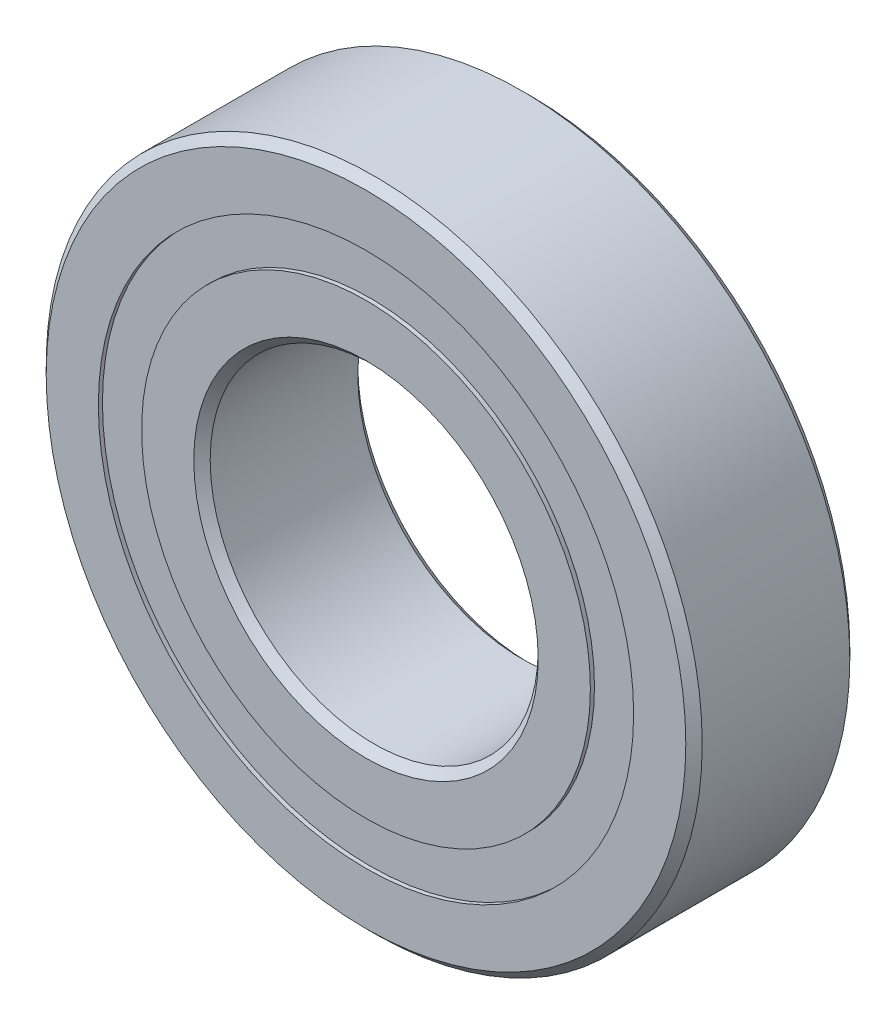
SolidWorks part; units mm, degrees
material "AISI 304"
ref_plane "Front Plane" through (0, 0, 0) normal (0, 0, 1) x (1, 0, 0)
ref_plane "Top Plane" through (0, 0, 0) normal (0, 1, 0) x (1, 0, 0)
ref_plane "Right Plane" through (0, 0, 0) normal (1, 0, 0) x (0, 0, -1)
sketch "Sketch1" plane through (0, 0, 0) normal (1, 0, 0) x (0, 0, -1)
  line L0 (-6.35, 0) -> (6.35, 0) construction
  line L1 (0, 25.4) -> (0, -25.4) construction
  line L2 (5.715, 25.4) -> (-5.715, 25.4)
  line L3 (-5.715, 25.4) -> (-6.35, 24.765)
  line L4 (-6.35, 24.765) -> (-6.35, 20.7247)
  line L5 (-6.35, 20.7247) -> (-2.8222, 20.7247)
  line L6 (6.35, 20.7247) -> (2.8222, 20.7247)
  line L7 (6.35, 24.765) -> (6.35, 20.7247)
  line L8 (5.715, 25.4) -> (6.35, 24.765)
  line L9 (0, 25.4) -> (0, 19.05) construction
  line L10 (0, 19.05) -> (0, 12.7) construction
  arc A0 (-2.8222, 20.7247) -> (2.8222, 20.7247) centre (0, 19.05) cw
  point P14 (0, 12.7)
  dimension "Width" = 12.7
  dimension "OD" = 50.8
  dimension "D1" = 45
  dimension "D2" = 0.635
  dimension "Shaft Dia" = 25.4
  dimension "D3" = 5.6444
  dimension "D4" = 1.6747
revolve "Revolve1" add sketch "Sketch1" angle 360 about L0
sketch "Sketch3" plane through (0, 0, 0) normal (1, 0, 0) x (0, 0, -1)
  line L0 (-6.35, 17.3753) -> (-2.8222, 17.3753)
  line L1 (0, 25.4) -> (0, -25.4) construction
  line L2 (-6.35, 24.765) -> (-6.35, 20.7247) construction
  line L3 (-6.35, 17.3753) -> (-6.35, 13.335)
  line L4 (-5.715, 25.4) -> (-6.35, 24.765) construction
  line L5 (-6.35, 13.335) -> (-5.715, 12.7)
  line L6 (-5.715, 12.7) -> (5.715, 12.7)
  line L7 (5.715, 25.4) -> (5.715, -25.4) construction
  line L8 (5.715, 12.7) -> (6.35, 13.335)
  line L9 (6.35, -24.765) -> (6.35, 24.765) construction
  line L10 (6.35, 13.335) -> (6.35, 17.3753)
  line L11 (6.35, 17.3753) -> (2.8222, 17.3753)
  line L13 (5.715, 25.4) -> (6.35, 24.765) construction
  arc A0 (2.8222, 20.7247) -> (-2.8222, 20.7247) centre (0, 19.05) ccw construction
  arc A1 (2.8222, 17.3753) -> (-2.8222, 17.3753) centre (0, 19.05) cw
revolve "Revolve3" add sketch "Sketch3" angle 360 about L0
sketch "Sketch4" plane through (0, 0, 0) normal (1, 0, 0) x (0, 0, -1)
  line L0 (-3.2817, 19.05) -> (3.2817, 19.05)
  arc A2 (-3.2817, 19.05) -> (3.2817, 19.05) centre (0, 19.05) cw
  arc A3 (2.8222, 20.7247) -> (-2.8222, 20.7247) centre (0, 19.05) ccw construction
revolve "Revolve4" add sketch "Sketch4" angle 360 about L0
ref_axis "Axis1" through (0, 0, -6.35) along (0, 0, 1)
pattern_circular "CirPattern1" count 12 every 30 about axis through (0, 0, -6.35) along (0, 0, 1) of bodies 104
sketch "Sketch5" plane through (0, 0, 0) normal (1, 0, 0) x (0, 0, -1)
  line L0 (-6.35, 20.7247) -> (-2.8222, 20.7247) construction
  line L1 (-6.0325, 20.7247) -> (-3.2817, 20.7247)
  line L2 (-6.0325, 20.7247) -> (-6.0325, 17.3753)
  line L3 (-6.0325, 17.3753) -> (-3.2817, 17.3753)
  line L4 (-3.2817, 20.7247) -> (-3.2817, 17.3753)
  line L5 (-6.35, 17.3753) -> (-2.8222, 17.3753) construction
  line L6 (6.35, 20.7247) -> (2.8222, 20.7247) construction
  line L7 (6.0325, 20.7247) -> (3.2817, 20.7247)
  line L8 (6.0325, 20.7247) -> (6.0325, 17.3753)
  line L9 (6.0325, 17.3753) -> (3.2817, 17.3753)
  line L10 (3.2817, 20.7247) -> (3.2817, 17.3753)
  line L11 (6.35, 17.3753) -> (2.8222, 17.3753) construction
  line L12 (-5.715, 25.4) -> (-6.35, 24.765) construction
  point P18 (-6.0325, 25.0825)
revolve "Revolve5" add sketch "Sketch5" angle 360 about L0
equation "\"D2@Sketch1\" = \"Width@Sketch1\"*.05"
equation "\"D3@Sketch1\" = \"Width@Sketch1\"/2.25"
equation "\"D4@Sketch1\" = (((\"OD@Sketch1\"-\"Width@Sketch1\")/2)/3.25)/3.5"
equation "\"D2@CirPattern1\" = 360/\"Balls@CirPattern1\""
